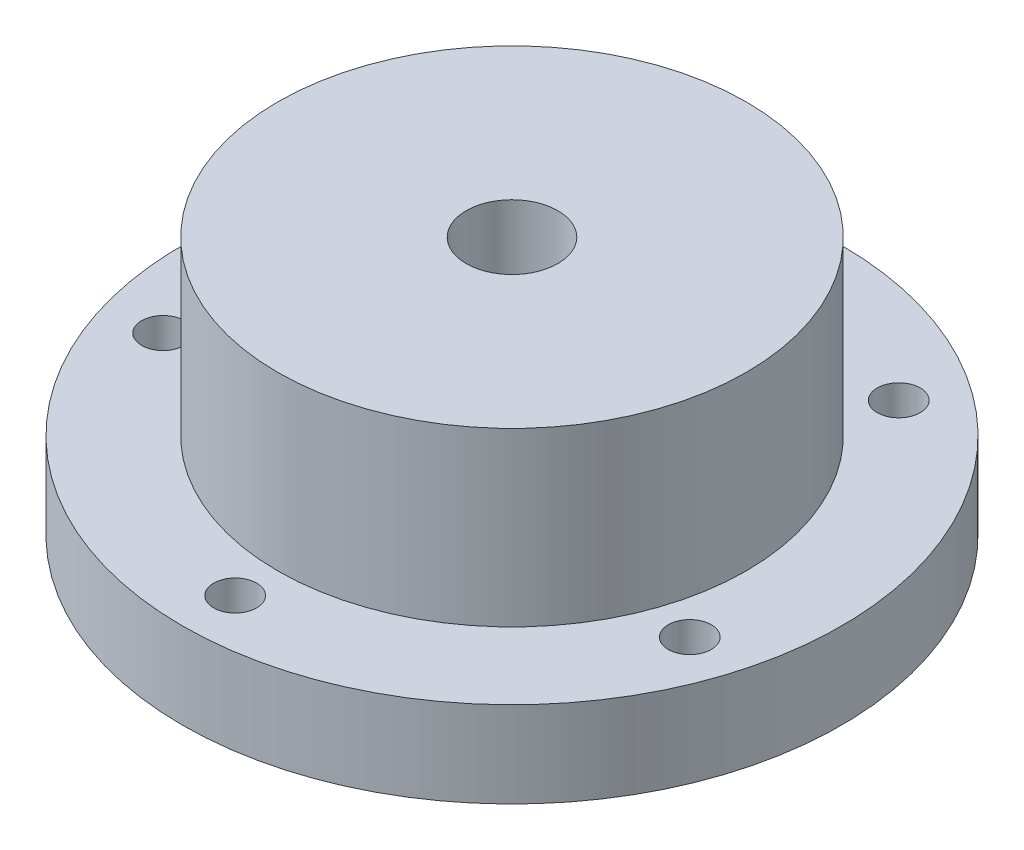
SolidWorks part; units mm, degrees
ref_plane "Front Plane" through (0, 0, 0) normal (0, 0, 1) x (1, 0, 0)
ref_plane "Top Plane" through (0, 0, 0) normal (0, 1, 0) x (1, 0, 0)
ref_plane "Right Plane" through (0, 0, 0) normal (1, 0, 0) x (0, 0, -1)
sketch "Sketch1" plane through (0, 0, 0) normal (0, 1, 0) x (1, 0, 0)
  circle A0 centre (0, 0) radius 1.6
  circle A1 centre (0, 0) radius 8.175
  circle A2 centre (0, 0) radius 11.5
  point P25 (0, 0)
extrude "Boss-Extrude1" add sketch "Sketch1" along normal blind 6 and the other way blind 3 contours A1 A0 region at (-7.9438, 0, 0)
extrude "Boss-Extrude2" add sketch "Sketch1<3>" against normal blind 3 separate body contours A2 A1 region at (-11.1747, 0, 0)
sketch "Sketch1<3>" plane through (0, 0, 0) normal (0, 1, 0) x (1, 0, 0) same geometry as "Sketch1"
sketch "Sketch2" plane through (0, 0, 0) normal (1, 0, 0) x (0, 0, -1)
  line L0 (0, 0) -> (0, 2)
  line L1 (0, 4) -> (0, 6)
  circle A0 centre (0, 3) radius 1
  dimension "D1" = 2
extrude "Cut-Extrude1" cut sketch "Sketch2" against normal blind 15 contours A0
sketch "Sketch3" plane through (0, -3, 0) normal (0, -1, 0) x (1, 0, 0)
  circle A0 centre (0, 9.6613) radius 0.75
  circle A2 centre (9.1884, 2.9855) radius 0.75
  circle A3 centre (5.6787, -7.8161) radius 0.75
  circle A4 centre (-5.6787, -7.8161) radius 0.75
  circle A5 centre (-9.1884, 2.9855) radius 0.75
  point P14 (0, 0)
  dimension "D1" = 5
sketch "Sketch4" plane through (0, -3, 0) normal (0, -1, 0) x (1, 0, 0)
  circle A0 centre (0, 0) radius 3.5
extrude "Boss-Extrude3" add sketch "Sketch4" along normal blind 5 contours A0
extrude "Cut-Extrude2" cut sketch "Sketch1<7>" against normal blind 13 contours A0
sketch "Sketch1<7>" plane through (0, 0, 0) normal (0, 1, 0) x (1, 0, 0) same geometry as "Sketch1"
extrude "Cut-Extrude3" cut sketch "Sketch3" against normal blind 10
